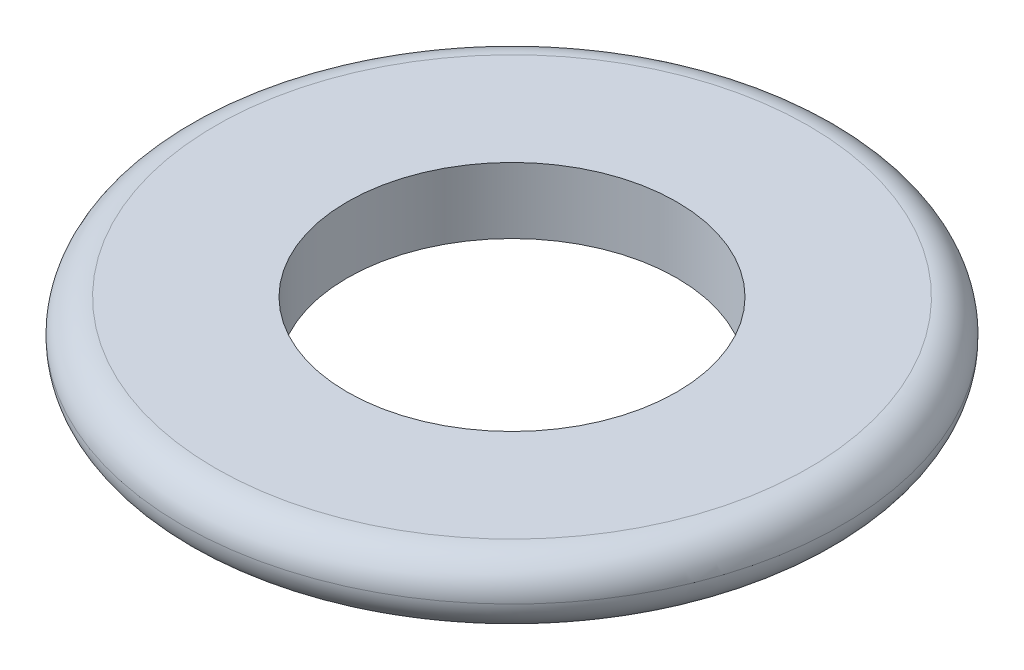
SolidWorks part; units mm, degrees
ref_plane "前视基准面" through (0, 0, 0) normal (0, 0, 1) x (1, 0, 0)
ref_plane "上视基准面" through (0, 0, 0) normal (0, 1, 0) x (1, 0, 0)
ref_plane "右视基准面" through (0, 0, 0) normal (1, 0, 0) x (0, 0, -1)
sketch "草图1" plane through (0, 0, 0) normal (0, 1, 0) x (1, 0, 0)
  circle A0 centre (0, 0) radius 5
  circle A1 centre (0, 0) radius 2.5
  dimension "D1" = 5
  dimension "D2" = 10
extrude "凸台-拉伸1" add sketch "草图1" along normal blind 1
fillet "圆角1" radius 0.5 2 edges at (0, 0, 5) (0, 1, 5)
